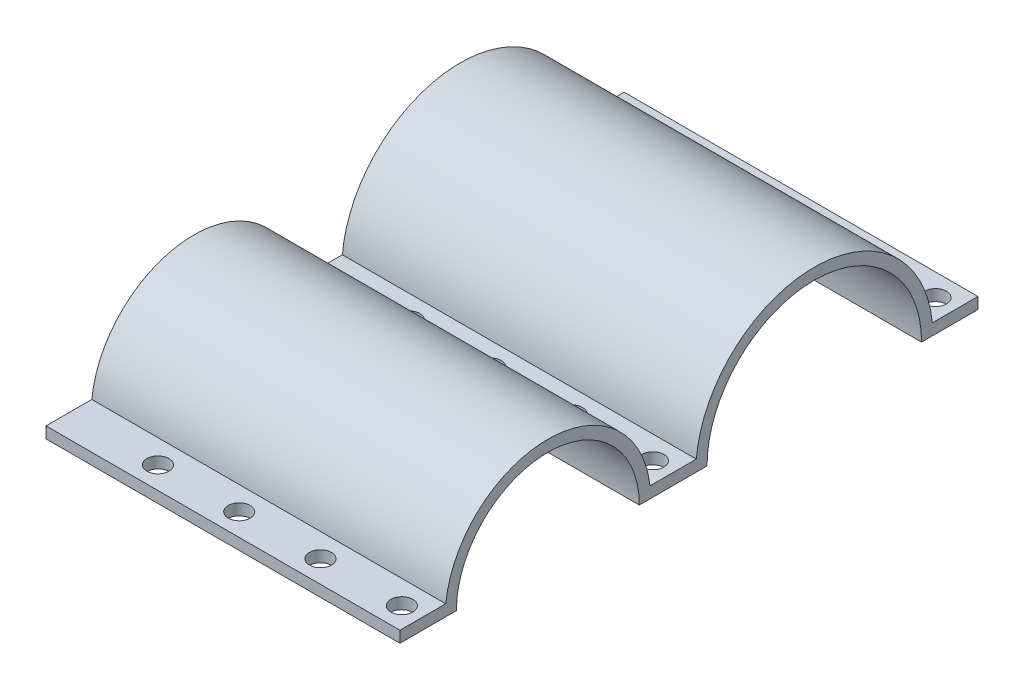
SolidWorks part; units mm, degrees
ref_plane "Front Plane" through (0, 0, 0) normal (0, 0, 1) x (1, 0, 0)
ref_plane "Top Plane" through (0, 0, 0) normal (0, 1, 0) x (1, 0, 0)
ref_plane "Right Plane" through (0, 0, 0) normal (1, 0, 0) x (0, 0, -1)
sketch "Sketch2" plane through (0, 0, 0) normal (1, 0, 0) x (0, 0, -1)
  line L0 (0, 0) -> (-10, 0)
  line L1 (-102.4, 0) -> (-102.4, 2)
  line L3 (0, 2) -> (0, 0)
  line L4 (-48, 0) -> (-60, 0)
  line L5 (-92.4, 0) -> (-102.4, 0)
  line L6 (0, 2) -> (-8.0955, 2)
  line L7 (-49.9045, 2) -> (-58.1102, 2)
  line L8 (-94.2898, 2) -> (-102.4, 2)
  line L9 (-102.4, 0) -> (-92.4, 0) construction
  line L10 (-102.4, 0) -> (-92.4, 0) construction
  arc A0 (-60, 0) -> (-92.4, 0) centre (-76.2, 0) ccw
  arc A1 (-10, 0) -> (-48, 0) centre (-29, 0) ccw
  arc A2 (-8.0955, 2) -> (-49.9045, 2) centre (-29, 0) ccw
  arc A3 (-58.1102, 2) -> (-94.2898, 2) centre (-76.2, 0) ccw
  point P4 (-76.2, 16.2)
  point P5 (-92.4671, 0)
  point P9 (-94.6404, 0)
  point P12 (-93.2673, 0)
  point P23 (0, 0)
  dimension "D2" = 16.2
  dimension "D4" = 19
  dimension "D3" = 10
  dimension "D6" = 2
extrude "Boss-Extrude1" add sketch "Sketch2" along normal blind 62.7
sketch "Sketch3" plane through (0, 2, 0) normal (0, 1, 0) x (1, 0, 0)
  line L1 (62.7, 0) -> (0, 0) construction
  line L2 (73.5, -3.93) -> (1.5, -3.93) construction
  line L6 (62.7, -102.4) -> (0, -102.4) construction
  line L7 (0, -60) -> (0, -48) construction
  line L8 (0, -54) -> (85.8213, -54) construction
  line L9 (0, -98.47) -> (85.8213, -98.47) construction
  line L10 (0, -60) -> (0, -48) construction
  circle A0 centre (15.9, -3.93) radius 1.95
  circle A1 centre (30.3, -3.93) radius 1.95
  circle A2 centre (44.7, -3.93) radius 1.95
  circle A3 centre (59.1, -3.93) radius 1.95
  circle A4 centre (15.9, -54) radius 1.95
  circle A5 centre (30.3, -54) radius 1.95
  circle A6 centre (44.7, -54) radius 1.95
  circle A7 centre (59.1, -54) radius 1.95
  circle A8 centre (15.9, -98.47) radius 1.95
  circle A9 centre (30.3, -98.47) radius 1.95
  circle A10 centre (44.7, -98.47) radius 1.95
  circle A11 centre (59.1, -98.47) radius 1.95
  point P40 (0, -54)
  dimension "D1" = 3.9
  dimension "D4" = 14.4
  dimension "D5" = 14.4
  dimension "D6" = 14.4
  dimension "D2" = 72
  dimension "D3" = 14.4
  dimension "D7" = 3.93
  dimension "D8" = 3.93
extrude "Cut-Extrude1" cut sketch "Sketch3" against normal up to surface (2 mm away) up to face at (31.35, 0, 97.4)
equation "\"MotorDIA\"= 37'ME 405 Motor Diameter"
equation "\"SyringeDIA\"= 31.4'60ml Syringe Diameter"
equation "\"MotorShaftDIA\"= 6'Motor Shaft Dia"
equation "\"MotorKeyway\"= 1'ME 405 Motor Shaft Keyway Depth"
equation "\"MotorLength\"= 56.7'ME 405 Motor Length Excluding Shaft"
equation "\"SyringeLength\"= 117.3'60ml Syringe Length Excluding Nozzle"
equation "\"3Dtol\"= .5'Sizing Tolerance for 3D printed parts"
equation "\"ChamberDIA\"= 100 - 4'Buoyancy Chamber inner Diameter"
equation "\"ChamberThk\"= 2mm'Buoyancy Chamber Wall Thickness"
equation "\"BearingOD\"= 10"
equation "\"BearingID\"= 4"
equation "\"Bearingwidth\"= 4"
equation "\"ShaftDIA\"= 4"
equation "\"D1@Boss-Extrude1\"=\"MotorLength\"+6"
equation "\"D4@Sketch3\"=\"D3@Sketch3\""
equation "\"D5@Sketch3\"=\"D3@Sketch3\""
equation "\"D6@Sketch3\"=\"D3@Sketch3\""
equation "\"D3@Sketch3\"=\"D2@Sketch3\"/5"
equation "\"D2@Sketch2\"=\"SyringeDIA\"/2+\"3Dtol\""
equation "\"D4@Sketch2\"=\"MotorDIA\"/2 + \"3Dtol\""
